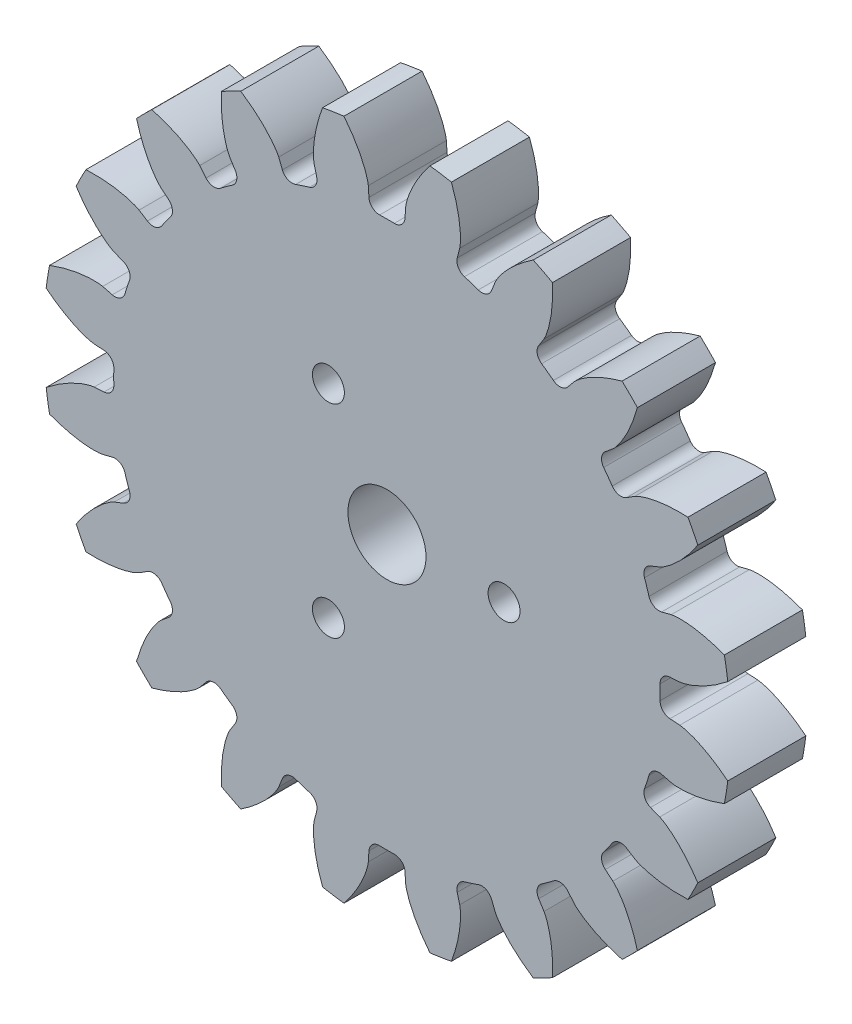
SolidWorks part; units mm, degrees
ref_plane "Front Plane" through (0, 0, 0) normal (0, 0, 1) x (1, 0, 0)
ref_plane "Top Plane" through (0, 0, 0) normal (0, 1, 0) x (1, 0, 0)
ref_plane "Right Plane" through (0, 0, 0) normal (1, 0, 0) x (0, 0, -1)
sketch "Sketch1" plane through (0, 0, 0) normal (0, 0, 1) x (1, 0, 0)
  line L0 (0, 0) -> (0, 25.4) construction
  line L1 (-8.1634, 28.3712) -> (8.1634, 22.4288) construction
  circle A0 centre (0, 0) radius 22.225 construction
  circle A1 centre (0, 0) radius 27.94 construction
  circle A2 centre (0, 0) radius 25.4 construction
  circle A3 centre (0, 0) radius 23.8682 construction
  circle A4 centre (0, 0) radius 3.175 construction
  circle A5 centre (0, 0) radius 37.465 construction
  point P8 (127, 0)
  point P13 (254, 0)
  dimension "OD | Outside Diameter" = 55.88
  dimension "Root Diameter" = 44.45
  dimension "Gear Pitch Diameter" = 50.8
  dimension "Base Diameter" = 47.7364
  dimension "For Shaft Diameter" = 6.35
  dimension "Hub Diameter" = 74.93
  dimension "Pressure Angle" = 20
  dimension "Number of Teeth" = 508
  dimension "Gear Pitch | Diametral Pitch" = 254
sketch "Sketch2" plane through (0, 0, 0) normal (1, 0, 0) x (0, 0, -1)
  line L0 (-3.175, 0) -> (3.175, 0) construction
  line L1 (-3.175, 27.94) -> (3.175, 27.94) construction
  point P2 (0, 27.94)
  point P4 (-3.175, 0)
  point P6 (-3.175, 27.94)
  dimension "Overall Width" = 6.35
  dimension "Hub Width" = 0
  dimension "Face Width" = 6.35
sketch "Sketch3" plane through (0, 0, 0) normal (0, 0, 1) x (1, 0, 0)
  circle A0 centre (0, 0) radius 27.94
  circle A1 centre (0, 0) radius 27.94 construction
extrude "Boss-Extrude1" add sketch "Sketch3" against normal up to vertex (3.175 mm away) and the other way up to vertex (3.175 mm away) up to point (0, 0, -3.175) other way up to point (0, 0, 3.175)
sketch "Sketch5" plane through (0, 0, 0) normal (1, 0, 0) x (0, 0, -1)
  line L11 (3.175, 3.175) -> (-3.175, 3.175)
  line L12 (3.175, 3.175) -> (3.175, 0)
  line L13 (3.175, 0) -> (-3.175, 0)
  line L14 (-3.175, 3.175) -> (-3.175, 0)
  point P5 (0, 3.175)
sketch "Sketch4" plane through (0, 0, 0) normal (0, 0, 1) x (1, 0, 0)
  line L0 (0, 0) -> (22.18, 1.4133) construction
  line L2 (0, 0) -> (22.18, -1.4133) construction
  line L4 (22.18, 1.4133) -> (23.8199, 1.5178)
  line L5 (23.8199, -1.5178) -> (22.18, -1.4133)
  arc A0 (22.18, 1.4133) -> (22.18, -1.4133) centre (0, 0) cw
  arc A3 (27.7203, 3.4971) -> (27.7203, -3.4971) centre (0, 0) cw
  circle A4 centre (0, 0) radius 27.94 construction
  spline S0 degree 4 poles (23.8199, 1.5178) (23.8264, 1.5183) (23.8447, 1.52) (23.8791, 1.5242) (23.9351, 1.5324) (24.0063, 1.5451) (24.098, 1.5639) (24.2056, 1.5892) (24.3234, 1.6202) (24.451, 1.6576) (24.5777, 1.698) (24.7036, 1.7411) (24.8285, 1.7868) (24.9791, 1.8451) (25.1589, 1.9193) (25.3675, 2.0122) (25.6024, 2.1249) (25.8398, 2.2475) (26.0717, 2.3744) (26.3039, 2.5099) (26.5271, 2.6462) (26.7567, 2.795) (26.9675, 2.9362) (27.2009, 3.1024) (27.3886, 3.2389) (27.6331, 3.4275) (27.7766, 3.5414) (27.9436, 3.6776) (28.0171, 3.7397) (28.0624, 3.7778) knots 0 0 0 0 0 0.005377 0.015084 0.028532 0.04661 0.064855 0.092111 0.119476 0.146842 0.174209 0.201575 0.228941 0.256307 0.307035 0.361767 0.4165 0.471232 0.525964 0.580697 0.635429 0.690161 0.744894 0.799626 0.854358 0.909091 0.954545 1 1 1 1 1 construction
  spline S1 degree 4 poles (23.8199, 1.5178) (23.8264, 1.5183) (23.8447, 1.52) (23.8791, 1.5242) (23.9351, 1.5324) (24.0063, 1.5451) (24.098, 1.5639) (24.2056, 1.5892) (24.3234, 1.6202) (24.451, 1.6576) (24.5777, 1.698) (24.7036, 1.7411) (24.8285, 1.7868) (24.9791, 1.8451) (25.1589, 1.9193) (25.3675, 2.0122) (25.6024, 2.1249) (25.8398, 2.2475) (26.0717, 2.3744) (26.3039, 2.5099) (26.5271, 2.6462) (26.7567, 2.795) (26.9675, 2.9362) (27.2009, 3.1024) (27.3886, 3.2389) (27.5801, 3.3866) (27.673, 3.4595) (27.7203, 3.4971) knots 0 0 0 0 0 0.005377 0.015084 0.028532 0.04661 0.064855 0.092111 0.119476 0.146842 0.174209 0.201575 0.228941 0.256307 0.307035 0.361767 0.4165 0.471232 0.525964 0.580697 0.635429 0.690161 0.744894 0.799626 0.854358 0.909091 0.909091 0.909091 0.909091 0.909091
  spline S2 degree 4 poles (23.8199, -1.5178) (23.8264, -1.5183) (23.8447, -1.52) (23.8791, -1.5242) (23.9351, -1.5324) (24.0063, -1.5451) (24.098, -1.5639) (24.2056, -1.5892) (24.3234, -1.6202) (24.451, -1.6576) (24.5777, -1.698) (24.7036, -1.7411) (24.8285, -1.7868) (24.9791, -1.8451) (25.1589, -1.9193) (25.3675, -2.0122) (25.6024, -2.1249) (25.8398, -2.2475) (26.0717, -2.3744) (26.3039, -2.5099) (26.5271, -2.6462) (26.7567, -2.795) (26.9675, -2.9362) (27.2009, -3.1024) (27.3886, -3.2389) (27.6331, -3.4275) (27.7766, -3.5414) (27.9436, -3.6776) (28.0171, -3.7397) (28.0624, -3.7778) knots 0 0 0 0 0 0.005377 0.015084 0.028532 0.04661 0.064855 0.092111 0.119476 0.146842 0.174209 0.201575 0.228941 0.256307 0.307035 0.361767 0.4165 0.471232 0.525964 0.580697 0.635429 0.690161 0.744894 0.799626 0.854358 0.909091 0.954545 1 1 1 1 1 construction
  spline S3 degree 4 poles (23.8199, -1.5178) (23.8264, -1.5183) (23.8447, -1.52) (23.8791, -1.5242) (23.9351, -1.5324) (24.0063, -1.5451) (24.098, -1.5639) (24.2056, -1.5892) (24.3234, -1.6202) (24.451, -1.6576) (24.5777, -1.698) (24.7036, -1.7411) (24.8285, -1.7868) (24.9791, -1.8451) (25.1589, -1.9193) (25.3675, -2.0122) (25.6024, -2.1249) (25.8398, -2.2475) (26.0717, -2.3744) (26.3039, -2.5099) (26.5271, -2.6462) (26.7567, -2.795) (26.9675, -2.9362) (27.2009, -3.1024) (27.3886, -3.2389) (27.5801, -3.3866) (27.673, -3.4595) (27.7203, -3.4971) knots 0 0 0 0 0 0.005377 0.015084 0.028532 0.04661 0.064855 0.092111 0.119476 0.146842 0.174209 0.201575 0.228941 0.256307 0.307035 0.361767 0.4165 0.471232 0.525964 0.580697 0.635429 0.690161 0.744894 0.799626 0.854358 0.909091 0.909091 0.909091 0.909091 0.909091
  dimension "D1" = 44.45
extrude "Cut-Extrude1" cut sketch "Sketch4" against normal through all both and the other way through all
fillet "Fillet1" radius 0.8522 2 edges at (22.18, -1.4133, 0) (22.18, 1.4133, 0)
pattern_circular "CirPattern1" count 20 over 360 about axis through (0, 0, 3.175) along (0, 0, -1) of "Cut-Extrude1", "Fillet1"
sketch "Sketch6" plane through (0, 0, 3.175) normal (0, 0, 1) x (1, 0, 0)
  circle A0 centre (9.525, 0) radius 1.3
  circle A1 centre (-4.7625, -8.2489) radius 1.3
  circle A2 centre (-4.7625, 8.2489) radius 1.3
  point P9 (0, 0)
  dimension "D2" = 2.6
  dimension "D1" = 9.525
  dimension "D3" = 3
extrude "Cut-Extrude2" cut sketch "Sketch6" against normal through all
sketch "Sketch7" plane through (0, 0, 3.175) normal (0, 0, 1) x (1, 0, 0)
  circle A0 centre (0, 0) radius 3.175
  dimension "D1" = 6.35
extrude "Cut-Extrude3" cut sketch "Sketch7" against normal through all
equation "\"Root Diameter@Sketch1\"=\"Root Diameter\""
equation "\"OD | Outside Diameter@Sketch1\"=\"Outside Diameter\""
equation "\"D1@CirPattern1\"=\"Number of Teeth\""
equation "\"Diametral Pitch\" = 10"
equation "\"Number of Teeth\"= 20"
equation "\"Pressure Angle\"=20"
equation "\"Pitch Diameter\"= \"Number of Teeth\" / \"Diametral Pitch\""
equation "\"Base Diameter\"= \"Pitch Diameter\" * cos ( \"Pressure Angle\" )"
equation "\"Outside Diameter\"= ( \"Number of Teeth\" + 2 ) / \"Diametral Pitch\""
equation "\"Dedendum\"= 1.25 / \"Diametral Pitch\""
equation "\"Root Diameter\"= \"Pitch Diameter\" - ( 2 * \"Dedendum\" )"
equation "\"Pitch Angle\"= 360deg / \"Number of Teeth\""
equation "\"Alpha\"= sqr ( \"Pitch Diameter\" ^ 2 - \"Base Diameter\" ^ 2 ) / \"Base Diameter\" * 180 / PI - \"Pressure Angle\""
equation "\"Beta\"= ( \"Pitch Angle\" / 4 - \"Alpha\" )"
equation "\"Phi\"= sqr ( ( \"Outside Diameter\" / 2 ) ^ 2 - ( \"Base Diameter\" / 2 ) ^ 2 ) / ( \"Base Diameter\" / 2 )"
equation "\"Addendum\"= 1 / \"Diametral Pitch\""
equation "\"WorkingDepth\"= 2 / \"Diametral Pitch\""
equation "\"WholeDepth\"= 2.25 / \"Diametral Pitch\""
equation "\"Clearance\"= 0.25 / \"Diametral Pitch\""
equation "\"ToothThickness\"= ( pi * 2 ) / \"Diametral Pitch\""
equation "\"CircularPitch\"= pi / \"Diametral Pitch\""
equation "\"Number of Teeth@Sketch1\"=\"Number of Teeth\""
equation "\"Gear Pitch | Diametral Pitch@Sketch1\"=\"Diametral Pitch\""
equation "\"Pressure Angle@Sketch1\"=\"Pressure Angle\""
equation "\"Gear Pitch Diameter@Sketch1\"=\"Pitch Diameter\""
equation "\"Base Diameter@Sketch1\"=\"Base Diameter\""
equation "\"Fillet\"= \"Clearance\" * cos ( \"Pressure Angle\" ) * tan ( ( 90 + \"Pressure Angle\" ) / 2 )"
equation "\"D1@Fillet1\"=\"Fillet\""
equation "\"D1@Sketch4\"=if( \"Base Diameter\">\"Root Diameter\",\"Root Diameter\",\"Base Diameter\"-.00001)"
equation "\"D2@Sketch6\"=2.6mm"
equation "\"tightTol\" = 0.005in"
equation "\"normTol\"= 0.01in"
equation "\"looseTol\"= 0.02in"
equation "\"D1@Sketch7\"=0.250000in"
